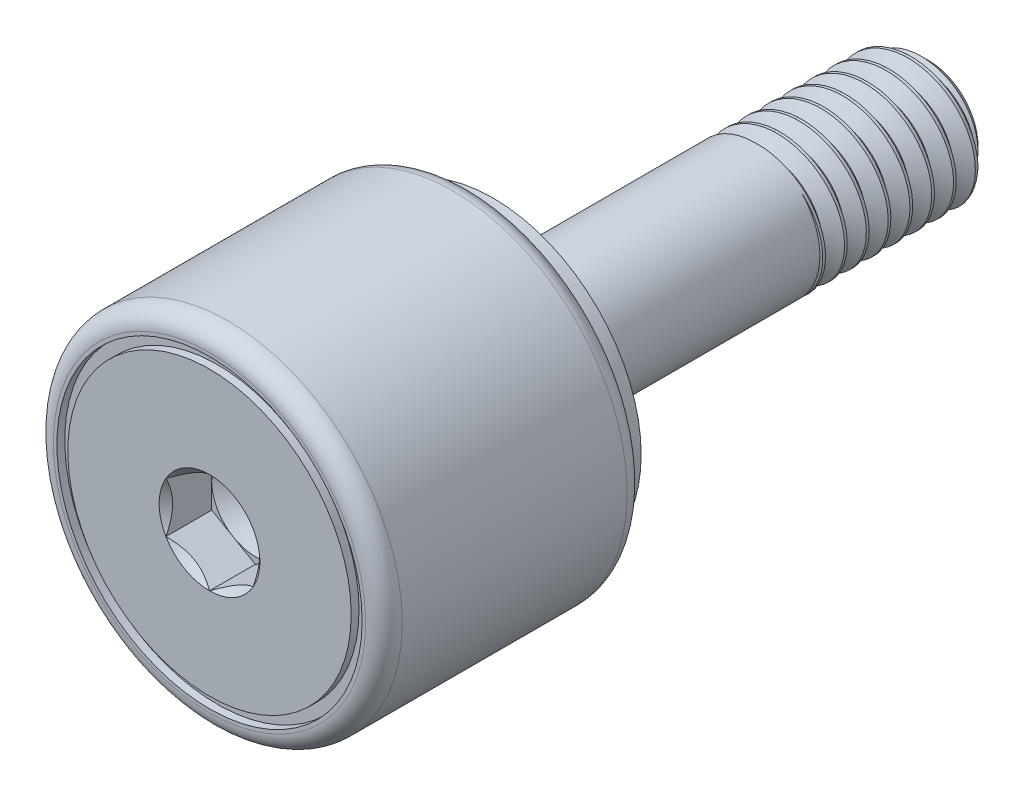
SolidWorks part; units mm, degrees
ref_plane "Front" through (0, 0, 0) normal (0, 0, 1) x (1, 0, 0)
ref_plane "Top" through (0, 0, 0) normal (0, 1, 0) x (1, 0, 0)
ref_plane "Right" through (0, 0, 0) normal (1, 0, 0) x (0, 0, -1)
sketch "Sketch1" plane through (0, 0, 0) normal (1, 0, 0) x (0, 0, -1)
  line L0 (0, 6.35) -> (9.525, 6.35)
  line L1 (9.525, 6.35) -> (9.525, 5.3975)
  line L2 (10.3188, 2.3813) -> (26.1938, 2.3813)
  line L3 (26.1938, 2.3813) -> (26.1938, 0)
  line L4 (26.1938, 0) -> (0, 0)
  line L5 (0, 0) -> (0, 6.35)
  line L6 (0, 6.35) -> (0, -6.35) construction
  line L7 (9.525, 5.3975) -> (10.3188, 5.3975)
  line L8 (10.3188, 5.3975) -> (10.3188, 2.3813)
  line L9 (10.3188, 5.3975) -> (10.3188, -5.3975) construction
  line L10 (26.1938, 2.3813) -> (26.1938, -2.3812) construction
  line L11 (26.1938, -2.3812) -> (10.3188, -2.3813) construction
  point P3 (10.3188, 0)
  point P11 (19.8438, 2.3813)
  point P13 (25.0031, -2.3813)
  dimension "D1" = 10.795
  dimension "B" = 9.525
  dimension "D2" = 1.1906
  dimension "A" = 12.7
  dimension "K" = 0.7937
  dimension "D" = 15.875
  dimension "C" = 4.7625
  dimension "E" = 6.35
revolve "Revolve1" add sketch "Sketch1" angle 360 about L4
sketch "Sketch2" plane through (0, 0, -26.1938) normal (0, 0, -1) x (-1, 0, 0)
  circle A1 centre (0, 0) radius 2.3813
  circle A2 centre (0, 0) radius 2.3813
  dimension "D1" = 0
curve "Helix/Spiral1" pitch 0.7937 height 7.1437 turns 9
sketch "Sketch3" plane through (0, 0, 0) normal (1, 0, 0) x (0, 0, -1)
  line L0 (26.1938, 2.3813) -> (26.8883, 2.3813)
  line L1 (26.8883, 2.3813) -> (26.5906, 1.8657)
  line L2 (26.5906, 1.8657) -> (26.4914, 1.8657)
  line L3 (26.4914, 1.8657) -> (26.1938, 2.3813)
  line L4 (26.3426, 2.1235) -> (26.7395, 2.1235) construction
  dimension "D1" = 60
  dimension "D2" = 0.3969
  dimension "D3" = 0.0992
chamfer "Chamfer1" distance 0.5953 angle 45 1 edges at (0, 2.3813, -26.1938)
sweep "Cut-Sweep1" cut profiles "Sketch3" path "Helix/Spiral1"
sketch "Sketch4" plane through (0, 0, -10.3188) normal (0, 0, -1) x (-1, 0, 0)
  circle A0 centre (0, 0) radius 2.3813 construction
  circle A1 centre (0, 0) radius 2.3813
extrude "Boss-Extrude1" add sketch "Sketch4" along normal up to vertex
sketch "Sketch5" plane through (0, 0, 0) normal (0, 0, 1) x (1, 0, 0)
  circle A0 centre (0, 0) radius 5.5562
  circle A1 centre (0, 0) radius 5.1594
  dimension "D1" = 11.1125
  dimension "D2" = 10.3187
extrude "Cut-Extrude1" cut sketch "Sketch5" against normal blind 0.2858
sketch "Sketch6" plane through (0, 0, 0) normal (0, 0, 1) x (1, 0, 0)
  line L1 (-1.5875, -0.9165) -> (0, -1.8331)
  line L2 (0, -1.8331) -> (1.5875, -0.9165)
  line L3 (1.5875, -0.9165) -> (1.5875, 0.9165)
  line L4 (1.5875, 0.9165) -> (0, 1.8331)
  line L5 (0, 1.8331) -> (-1.5875, 0.9165)
  line L6 (-1.5875, 0.9165) -> (-1.5875, -0.9165)
  circle A0 centre (0, 0) radius 1.5875 construction
  dimension "H Hex" = 3.175
extrude "Cut-Extrude2" cut sketch "Sketch6" against normal blind 1.6669
sketch "Sketch7" plane through (0, 0, 0) normal (0, 0, 1) x (1, 0, 0)
  circle A0 centre (0, 0) radius 1.8331
extrude "Cut-Extrude3" cut sketch "Sketch7" against normal through all draft 45
sketch "Sketch8" plane through (0, 0, -1.6669) normal (0, 0, 1) x (1, 0, 0)
  circle A0 centre (0, 0) radius 1.5875 construction
  circle A1 centre (0, 0) radius 1.5875
extrude "Cut-Extrude4" cut sketch "Sketch8" against normal through all draft 60
fillet "Fillet1" radius 0.6668 2 edges at (0, 6.35, -9.525) (0, 6.35, 0)
sketch "Sketch9" plane through (0, 0, 0) normal (1, 0, 0) x (0, 0, -1)
  line L0 (0, 0) -> (26.1938, 0) construction
  line L1 (26.1938, -1.7859) -> (26.1938, 1.7859) construction
  line L2 (0, 1.5875) -> (26.1938, 1.5875) construction
  line L3 (21.0445, 1.5875) -> (21.0445, 1.1392)
  line L4 (21.0445, 6.35) -> (21.0445, 1.5875)
  line L5 (21.0445, 6.35) -> (21.8209, 6.35)
  line L6 (21.8209, 6.35) -> (21.8209, 1.5875)
  line L8 (20.268, 6.35) -> (20.268, 1.5875) construction
  line L9 (10.3188, 5.3975) -> (10.3188, -5.3975) construction
  line L10 (21.0445, 1.1392) -> (21.8209, 1.5875)
  dimension "D3" = 4.7625
  dimension "I Radial Hole Dia" = 1.5529
  dimension "J Hole Center Dist" = 10.7257
  dimension "D1" = 1.5875
  dimension "D2" = 60
  dimension "D4" = 0.4483
revolve "Cut-Revolve1" [suppressed] cut sketch "Sketch9" angle 360 about L4
equation "\"D1@Sketch1\" = \"A@Sketch1\" * .85"
equation "\"D3@Helix/Spiral1\" = \"E@Sketch1\" + \"D4@Helix/Spiral1\""
equation "\"D3@Sketch3\" = \"D4@Helix/Spiral1\" * .125"
equation "\"D2@Sketch3\" = \"D4@Helix/Spiral1\" * .5"
equation "\"D1@Chamfer1\" = \"D4@Helix/Spiral1\" * .75"
equation "\"D1@Sketch5\" = \"A@Sketch1\" * .875"
equation "\"D2@Sketch5\" = \"A@Sketch1\" * .8125"
equation "\"D1@Cut-Extrude1\" = \"B@Sketch1\" * .03"
equation "\"D1@Cut-Extrude2\" = \"C@Sketch1\" * .35"
equation "\"D1@Fillet1\" = \"B@Sketch1\" * .07"
equation "\"D2@Sketch1\" = \"D4@Helix/Spiral1\" * 1.5"
equation "\"D3@Sketch9\" = \"C@Sketch1\""
equation "\"D1@Sketch9\" = \"H Hex@Sketch6\" / 2"
